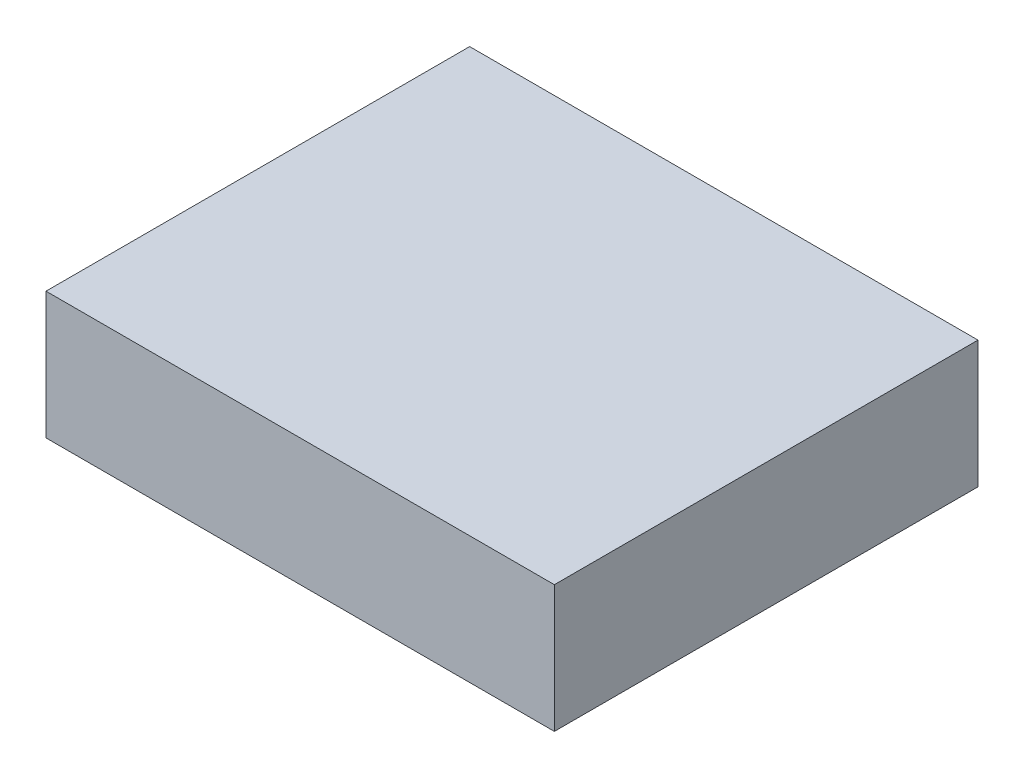
SolidWorks part; units mm, degrees
material "Cast Alloy Steel"
ref_plane "Front Plane" through (0, 0, 0) normal (1, 0, 0) x (0, 1, 0)
ref_plane "Top Plane" through (0, 0, 0) normal (0, 0, 1) x (0, 1, 0)
ref_plane "Right Plane" through (0, 0, 0) normal (0, 1, 0) x (-1, 0, 0)
sketch "Sketch1" plane through (0, 0, 0) normal (1, 0, 0) x (0, 1, 0)
  line L1 (0, -55) -> (0, 55) construction
  line L2 (-450, 150) -> (0, 150)
  line L3 (-450, 150) -> (-450, 0)
  line L4 (-450, 0) -> (0, 0)
  line L5 (0, 150) -> (0, 0)
  line L6 (0, 150) -> (150, 150)
  line L7 (0, 150) -> (0, 1150)
  line L8 (0, 1150) -> (150, 1150)
  line L9 (150, 150) -> (150, 1150)
  line L10 (-450, 0) -> (-480, 0)
  line L11 (-450, 0) -> (-450, -100)
  line L12 (-450, -100) -> (-480, -100)
  line L13 (-480, 0) -> (-480, -100)
  line L14 (55, 0) -> (-55, 0) construction
  dimension "D1" = 1000
  dimension "D2" = 150
  dimension "D3" = 30
  dimension "D4" = 150
  dimension "D5" = 450
  dimension "D6" = 100
  dimension "D7" = 0
  dimension "D8" = 0
extrude "Boss-Extrude2" add sketch "Sketch1" along normal blind 60 and the other way blind 60 contours L10 L13 L12 L11 region at (0, -465, -50)
